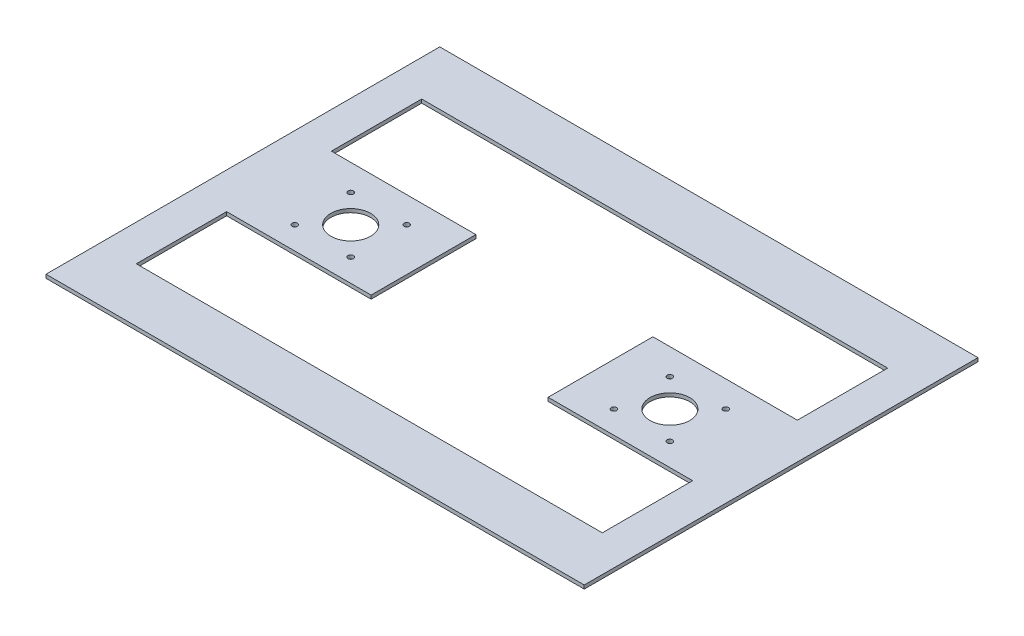
SolidWorks part; units mm, degrees
ref_plane "Front Plane" through (0, 0, 0) normal (0, 0, 1) x (1, 0, 0)
ref_plane "Top Plane" through (0, 0, 0) normal (0, 1, 0) x (1, 0, 0)
ref_plane "Right Plane" through (0, 0, 0) normal (1, 0, 0) x (0, 0, -1)
sketch "Sketch1" plane through (0, 0, 0) normal (1, 0, 0) x (0, 0, -1)
  line L0 (-26.6783, 0) -> (191.3217, 0)
  line L1 (119.9, 0) -> (-119.9, 0) construction
  line L2 (-26.6783, 0) -> (-26.6783, 2)
  line L3 (191.3217, 0) -> (191.3217, 2)
  line L4 (191.3217, 2) -> (-26.6783, 2)
  dimension "D1" = 218
  dimension "D2" = 2
extrude "Boss-Extrude1" add sketch "Sketch1" along normal blind 298 contours L4 L2 L0 L3
sketch "Sketch2" plane through (0, 2, 0) normal (0, 1, 0) x (1, 0, 0)
  line L0 (0, -1.1) -> (0, 1.1) construction
  line L1 (20, 161.3217) -> (278, 161.3217)
  line L2 (20, 161.3217) -> (20, 111.3217)
  line L3 (20, 3.3217) -> (278, 3.3217)
  line L4 (278, 161.3217) -> (278, 111.3217)
  line L5 (298, 191.3217) -> (298, -26.6783) construction
  line L6 (298, -26.6783) -> (0, -26.6783) construction
  line L7 (298, 191.3217) -> (0, 191.3217) construction
  line L8 (20, 111.3217) -> (100, 111.3217)
  line L9 (100, 111.3217) -> (100, 53.3217)
  line L10 (100, 53.3217) -> (20, 53.3217)
  line L12 (20, 53.3217) -> (20, 3.3217)
  line L13 (278, 53.3217) -> (278, 3.3217)
  line L14 (198, 111.3217) -> (278, 111.3217)
  line L15 (198, 111.3217) -> (198, 53.3217)
  line L16 (198, 53.3217) -> (278, 53.3217)
  line L18 (60.6504, 81.3768) -> (364.4406, 81.3768) construction
  line L19 (364.4406, 81.3768) -> (-100.6938, 81.3768) construction
  line L20 (149, 244.2227) -> (149, -99.356) construction
  circle A0 centre (60.6504, 81.3768) radius 11
  circle A4 centre (76.1504, 65.8768) radius 1.5
  circle A5 centre (45.1504, 65.8768) radius 1.5
  circle A6 centre (76.1504, 96.8768) radius 1.5
  circle A7 centre (45.1504, 96.8768) radius 1.5
  circle A8 centre (252.8496, 65.8768) radius 1.5
  circle A9 centre (221.8496, 65.8768) radius 1.5
  circle A10 centre (221.8496, 96.8768) radius 1.5
  circle A11 centre (252.8496, 96.8768) radius 1.5
  circle A12 centre (237.3496, 81.3768) radius 11
  dimension "D9" = 22
  dimension "D10" = 3
  dimension "D11" = 3
  dimension "D1" = 20
  dimension "D2" = 20
  dimension "D3" = 30
  dimension "D4" = 30
  dimension "D5" = 50
  dimension "D6" = 50
  dimension "D7" = 80
  dimension "D8" = 80
  dimension "D12" = 31
  dimension "D13" = 15.5
  dimension "D14" = 15.5
  dimension "D15" = 149
extrude "Cut-Extrude1" cut sketch "Sketch2" against normal blind 10
